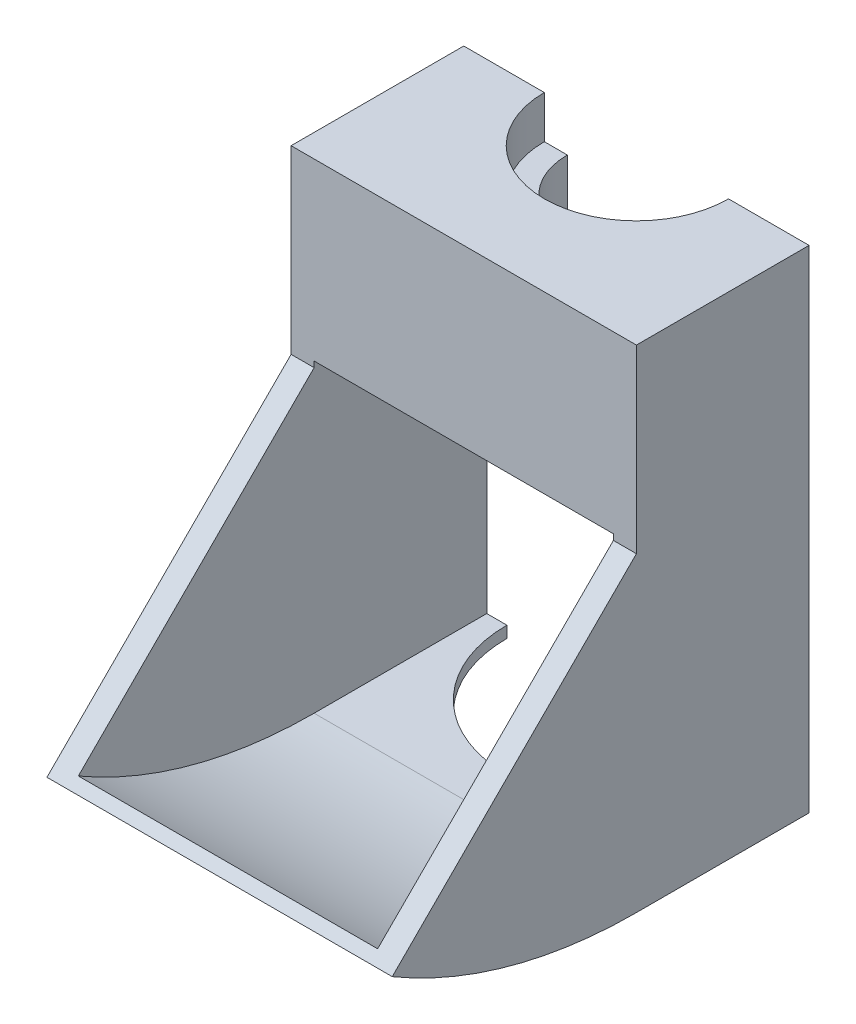
SolidWorks part; units mm, degrees
ref_plane "Front Plane" through (0, 0, 0) normal (0, 0, 1) x (1, 0, 0)
ref_plane "Top Plane" through (0, 0, 0) normal (0, 1, 0) x (1, 0, 0)
ref_plane "Right Plane" through (0, 0, 0) normal (1, 0, 0) x (0, 0, -1)
sketch "Sketch2" plane through (0, 0, 0) normal (0, 0, 1) x (1, 0, 0)
  line L1 (-15, 0) -> (15, 0)
  line L2 (-15, 0) -> (-15, 42.7)
  line L3 (-15, 42.7) -> (15, 42.7)
  line L4 (15, 0) -> (15, 42.7)
  line L5 (0, 42.7) -> (0, 0) construction
  line L6 (-15, 21.35) -> (15, 21.35) construction
  point P120 (0, 21.35)
  dimension "D1" = 30
  dimension "D2" = 42.7
extrude "Boss-Extrude1" add sketch "Sketch2" along normal blind 15
sketch "Sketch3" plane through (0, 0, 0) normal (1, 0, 0) x (0, 0, -1)
  line L0 (-15, 0) -> (-15, 42.7)
  line L1 (-15, 0) -> (-15, 42.7)
  line L2 (-15, 27) -> (-36.2132, 5.7868)
  line L3 (-15, 42.7) -> (-15, 0) construction
  line L4 (-15, 0) -> (0, 0) construction
  arc A0 (-36.2132, 5.7868) -> (-15, 0) centre (-15, 41.775) ccw
  dimension "D1" = 30
  dimension "D2" = 45
  dimension "D3" = 27
extrude "Boss-Extrude2" add sketch "Sketch3" along normal mid plane 30 contours L2 A0 L1 region at (0, 10.3238, 22.3306)
sketch "Sketch4" plane through (0, 0, 0) normal (0, 0, -1) x (-1, 0, 0)
  line L0 (0, 51.4794) -> (0, -30.0904) construction
  line L1 (0, 42.7) -> (8, 42.7)
  line L2 (8, 42.7) -> (8, 39)
  line L3 (8, 39) -> (6, 39)
  line L4 (6, 39) -> (6, 33)
  line L5 (6, 33) -> (8, 33)
  line L6 (8, 33) -> (8, 27.5)
  line L7 (-15, 42.7) -> (15, 42.7) construction
  line L8 (0, 0) -> (0, 42.7)
  line L10 (8, 27.5) -> (11.25, 27.5)
  line L11 (11.25, 27.5) -> (11.25, 0)
  line L12 (15, 0) -> (-15, 0) construction
  line L13 (11.25, 0) -> (0, 0)
  dimension "D1" = 16
  dimension "D2" = 12
  dimension "D3" = 3.7
  dimension "D4" = 6
  dimension "D5" = 5.5
  dimension "D6" = 22.5
revolve "Cut-Revolve1" cut sketch "Sketch4" angle 360 about L0
sketch "Sketch5" plane through (0, 0, 0) normal (1, 0, 0) x (0, 0, -1)
  line L0 (-35.4823, 6.5177) -> (-15.7071, 26.2929)
  line L1 (-15, 27) -> (-36.2132, 5.7868) construction
  line L2 (-15.7071, 26.2929) -> (-16.9142, 27.5)
  line L3 (-16.9142, 27.5) -> (-11.25, 27.5)
  line L4 (-11.25, 27.5) -> (0, 27.5) construction
  line L5 (-11.25, 27.5) -> (0, 27.5)
  line L6 (0, 27.5) -> (0, 1)
  line L7 (-15, 1) -> (0, 1)
  line L8 (-11.25, 0) -> (-15, 0)
  line L9 (-11.25, 0) -> (-15, 0) construction
  arc A0 (-15, 1) -> (-35.4823, 6.5177) centre (-15, 41.775) cw
  arc A1 (-36.2132, 5.7868) -> (-15, 0) centre (-15, 41.775) ccw
  arc A2 (-36.2132, 5.7868) -> (-15, 0) centre (-15, 41.775) ccw construction
  dimension "D1" = 1
  dimension "D2" = 1
extrude "Cut-Extrude1" cut sketch "Sketch5" against normal mid plane 26
